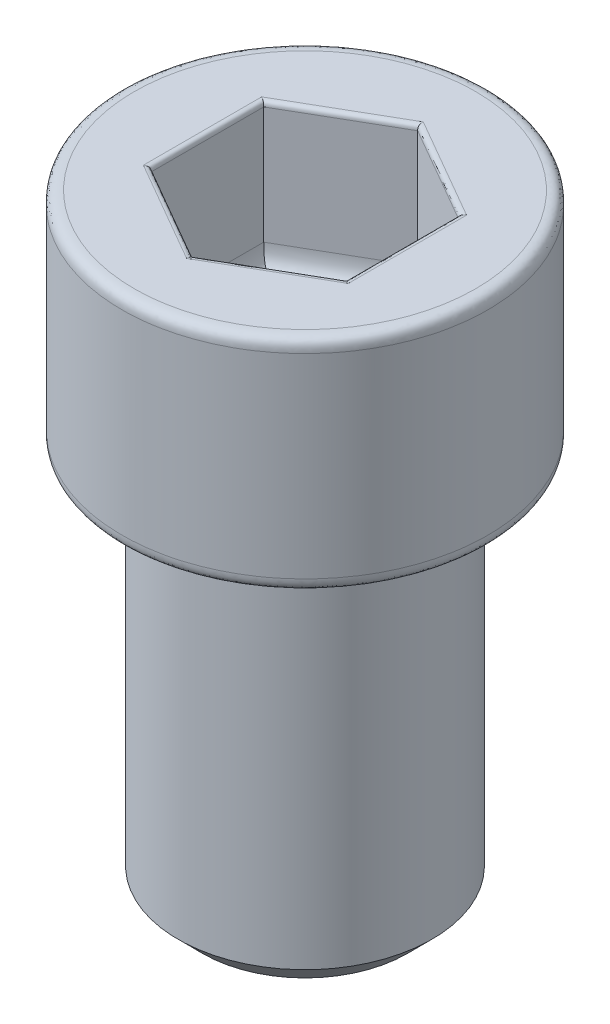
SolidWorks part; units mm, degrees
ref_plane "Front Plane" through (0, 0, 0) normal (0, 0, 1) x (1, 0, 0)
ref_plane "Top Plane" through (0, 0, 0) normal (0, 1, 0) x (1, 0, 0)
ref_plane "Right Plane" through (0, 0, 0) normal (1, 0, 0) x (0, 0, -1)
sketch "Sketch2" plane through (0, 0, 0) normal (1, 0, 0) x (0, 0, -1)
  line L0 (0, 0) -> (0, 25)
  line L1 (0, 25) -> (7.5, 25)
  line L2 (7.5, 25) -> (7.5, 16)
  line L3 (7.5, 16) -> (5.2, 16)
  line L4 (5.2, 16) -> (5.2, 0)
  line L5 (5.2, 0) -> (0, 0)
  dimension "D1" = 5.2
  dimension "D2" = 7.5
  dimension "D3" = 9
  dimension "D4" = 25
revolve "Revolve1" add sketch "Sketch2" angle 360 about L0
chamfer "Chamfer1" distance 1 angle 45 1 edges at (0, 0, -5.2)
sketch "Sketch3" plane through (0, 25, 0) normal (0, 1, 0) x (1, 0, 0)
  line L1 (0, 4.6188) -> (-4, 2.3094)
  line L2 (-4, 2.3094) -> (-4, -2.3094)
  line L3 (-4, -2.3094) -> (0, -4.6188)
  line L4 (0, -4.6188) -> (4, -2.3094)
  line L5 (4, -2.3094) -> (4, 2.3094)
  line L6 (4, 2.3094) -> (0, 4.6188)
  circle A0 centre (0, 0) radius 4 construction
  dimension "D1" = 8
extrude "Cut-Extrude1" cut sketch "Sketch3" against normal blind 6
fillet "Fillet1" radius 1 6 edges at (4, 19, 0) (2, 19, 3.4641) (-2, 19, 3.4641) (-4, 19, 0) (-2, 19, -3.4641) (2, 19, -3.4641) curvature continuous yes
fillet "Fillet2" radius 0.5 2 edges at (0, 16, -7.5) (0, 25, -7.5) curvature continuous yes
ref_axis "Axis1" through (0, 36, 0) along (0, -1, 0)
fillet "Fillet3" radius 0.2 6 edges at (-4, 25, 0) (-2, 25, 3.4641) (2, 25, 3.4641) (4, 25, 0) (2, 25, -3.4641) (-2, 25, -3.4641) curvature continuous yes
